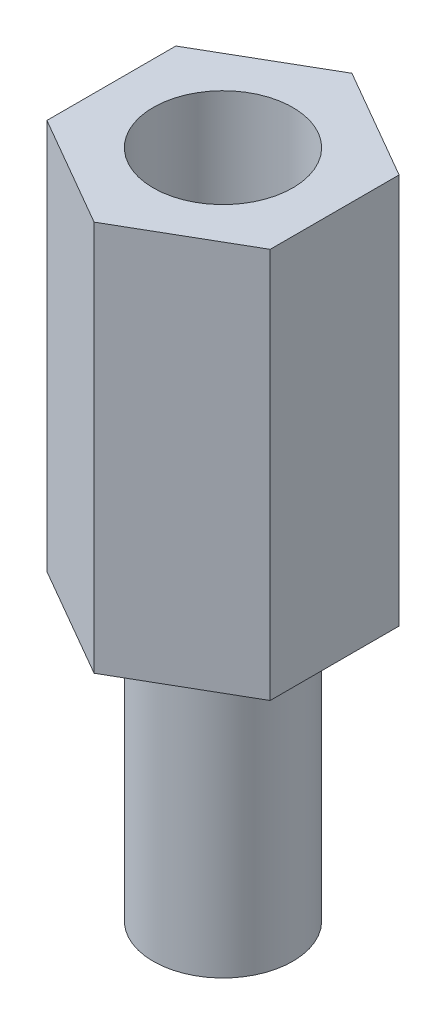
SolidWorks part; units mm, degrees
ref_plane "Front Plane" through (0, 0, 0) normal (0, 0, 1) x (1, 0, 0)
ref_plane "Top Plane" through (0, 0, 0) normal (0, 1, 0) x (1, 0, 0)
ref_plane "Right Plane" through (0, 0, 0) normal (1, 0, 0) x (0, 0, -1)
sketch "Sketch1" plane through (0, 0, 0) normal (0, 1, 0) x (1, 0, 0)
  line L1 (0, 4.6188) -> (-4, 2.3094)
  line L2 (-4, 2.3094) -> (-4, -2.3094)
  line L3 (-4, -2.3094) -> (0, -4.6188)
  line L4 (0, -4.6188) -> (4, -2.3094)
  line L5 (4, -2.3094) -> (4, 2.3094)
  line L6 (4, 2.3094) -> (0, 4.6188)
  circle A0 centre (0, 0) radius 4 construction
  circle A1 centre (0, 0) radius 2.5
  dimension "D2" = 5
  dimension "D1" = 8
extrude "Boss-Extrude1" add sketch "Sketch1" along normal blind 14 contours L4 L5 L6 L1 L2 L3
extrude "Boss-Extrude2" add sketch "Sketch1<3>" against normal blind 10 contours A1 region at (0, 0, 0)
sketch "Sketch1<3>" plane through (0, 0, 0) normal (0, 1, 0) x (1, 0, 0) same geometry as "Sketch1"
sketch "Sketch3" plane through (0, 14, 0) normal (0, 1, 0) x (1, 0, 0)
  circle A0 centre (0, 0) radius 2.5
  dimension "D1" = 5
extrude "Cut-Extrude1" cut sketch "Sketch3" against normal blind 6
